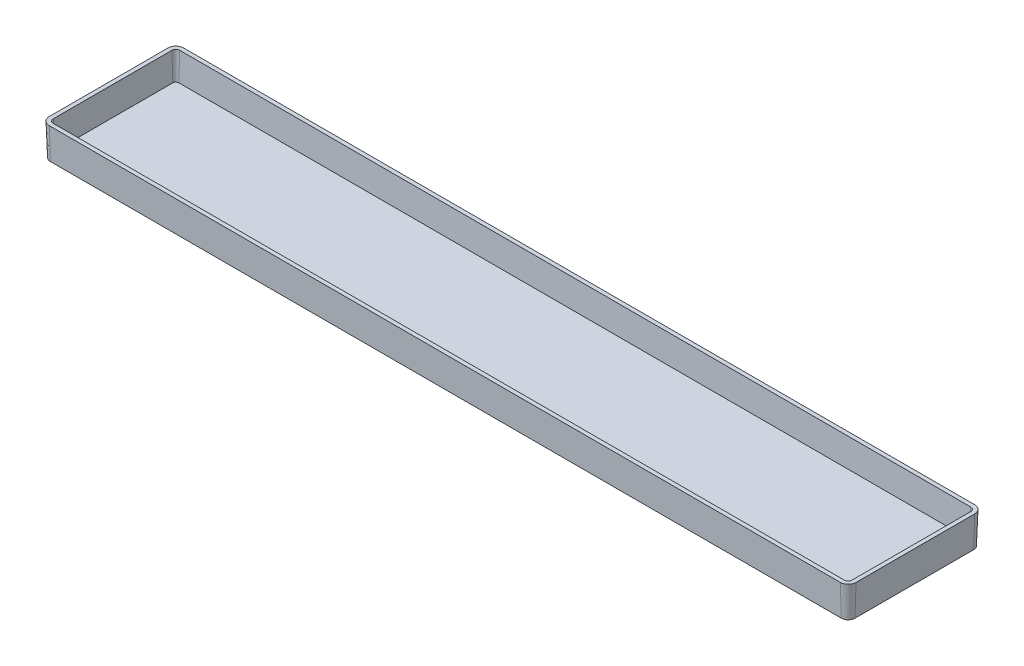
SolidWorks part; units mm, degrees
ref_plane "Front Plane" through (0, 0, 0) normal (0, 0, 1) x (1, 0, 0)
ref_plane "Top Plane" through (0, 0, 0) normal (0, 1, 0) x (1, 0, 0)
ref_plane "Right Plane" through (0, 0, 0) normal (1, 0, 0) x (0, 0, -1)
sketch "Sketch1" plane through (0, 0, 0) normal (0, 1, 0) x (1, 0, 0)
  line L1 (-50, -8.5) -> (50, -8.5)
  line L2 (-51, -7.5) -> (-51, 7.5)
  line L3 (-50, 8.5) -> (50, 8.5)
  line L4 (51, -7.5) -> (51, 7.5)
  line L5 (-51, -8.5) -> (51, 8.5) construction
  line L6 (-51, 8.5) -> (51, -8.5) construction
  arc A0 (-51, 7.5) -> (-50, 8.5) centre (-50, 7.5) cw
  arc A1 (51, 7.5) -> (50, 8.5) centre (50, 7.5) ccw
  arc A2 (51, -7.5) -> (50, -8.5) centre (50, -7.5) cw
  arc A3 (-50, -8.5) -> (-51, -7.5) centre (-50, -7.5) cw
  point P0 (0, 0)
  dimension "D3" = 1
  dimension "D1" = 102
  dimension "D2" = 17
extrude "Boss-Extrude1" add sketch "Sketch1" against normal blind 4 draft 2
shell "Shell1" thickness 0.5 removed face at (0, 0, 0)
